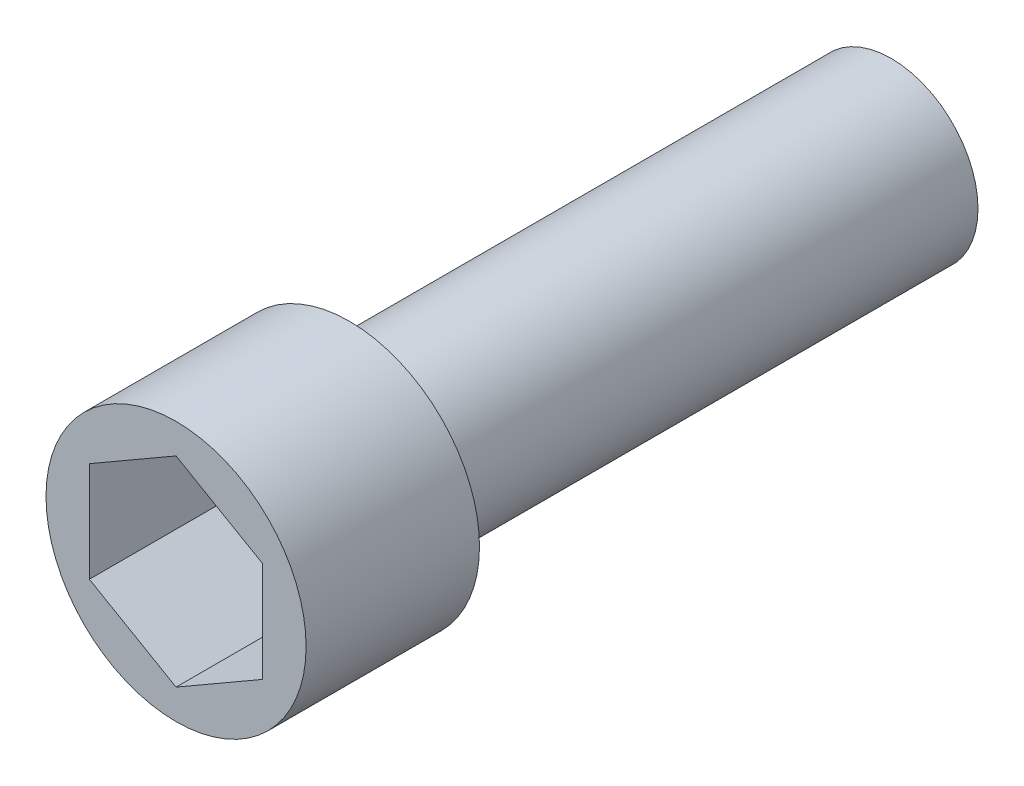
SolidWorks part; units mm, degrees
material "AISI 304"
ref_plane "Front Plane" through (0, 0, 0) normal (0, 0, 1) x (1, 0, 0)
ref_plane "Top Plane" through (0, 0, 0) normal (0, 1, 0) x (1, 0, 0)
ref_plane "Right Plane" through (0, 0, 0) normal (1, 0, 0) x (0, 0, -1)
sketch "Sketch1" plane through (0, 0, 0) normal (0, 0, 1) x (1, 0, 0)
  line L1 (0, 4.6188) -> (-4, 2.3094)
  line L2 (-4, 2.3094) -> (-4, -2.3094)
  line L3 (-4, -2.3094) -> (0, -4.6188)
  line L4 (0, -4.6188) -> (4, -2.3094)
  line L5 (4, -2.3094) -> (4, 2.3094)
  line L6 (4, 2.3094) -> (0, 4.6188)
  circle A0 centre (0, 0) radius 6
  circle A1 centre (0, 0) radius 4
  circle A2 centre (0, 0) radius 4 construction
  point P4 (0, 0)
  dimension "D2" = 8
  dimension "D3" = 12
  dimension "D1" = 8
extrude "Boss-Extrude1" add sketch "Sketch1" against normal blind 8 contours A0
extrude "Boss-Extrude2" add sketch "Sketch1<3>" against normal blind 33 contours A1
sketch "Sketch1<3>" plane through (0, 0, 0) normal (0, 0, 1) x (1, 0, 0) same geometry as "Sketch1"
extrude "Cut-Extrude1" cut sketch "Sketch1<4>" against normal blind 6 contours L1 L2 L3 L4 L5 L6
sketch "Sketch1<4>" plane through (0, 0, 0) normal (0, 0, 1) x (1, 0, 0) same geometry as "Sketch1"
